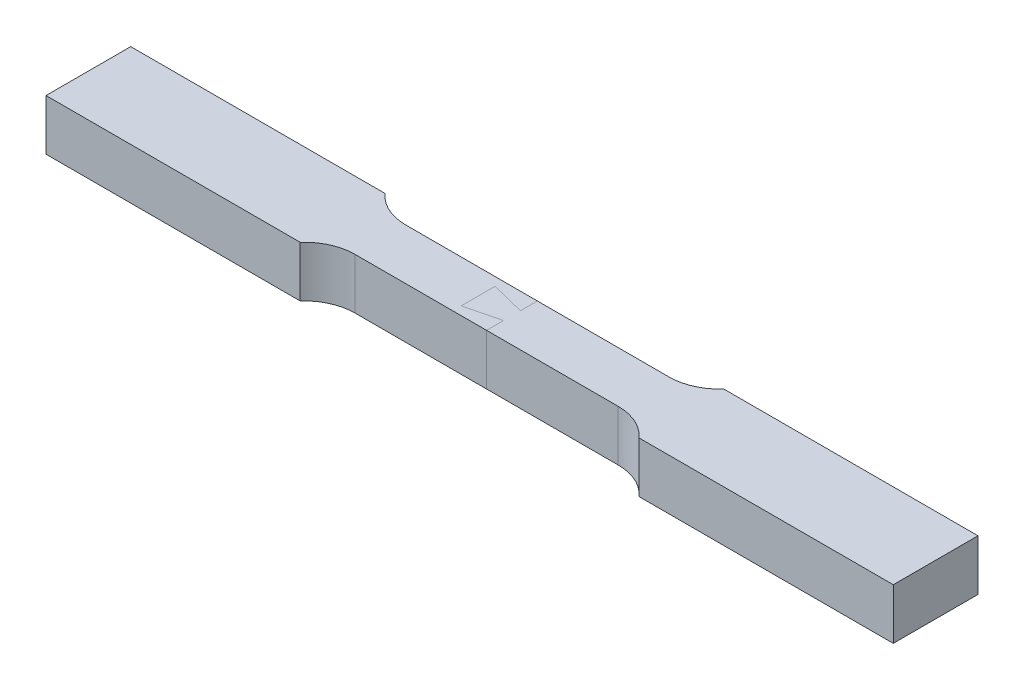
SolidWorks part; units mm, degrees
ref_plane "Front" through (0, 0, 0) normal (0, 0, 1) x (1, 0, 0)
ref_plane "Top" through (0, 0, 0) normal (0, 1, 0) x (1, 0, 0)
ref_plane "Right" through (0, 0, 0) normal (1, 0, 0) x (0, 0, -1)
sketch "Sketch1" plane through (0, 0, 0) normal (0, 1, 0) x (1, 0, 0)
  line L0 (0, 32.0696) -> (0, -21.7429) construction
  line L10 (15.5279, 3) -> (-15.5279, 3)
  line L11 (-4, 2) -> (0, 1)
  line L12 (-20, 5) -> (-50, 5)
  line L13 (-50, 5) -> (-50, -5)
  line L14 (-50, -5) -> (-20, -5)
  line L15 (-4, 2) -> (-4, -2)
  line L16 (-15.5279, -3) -> (15.5279, -3)
  line L17 (-50, 0) -> (0, 0) construction
  line L18 (-4, -2) -> (0, -1)
  line L19 (0, 3) -> (0, 1)
  line L20 (0, -3) -> (0, -1)
  line L21 (50, 5) -> (50, -5)
  line L22 (50, -5) -> (20, -5)
  line L23 (20, 5) -> (50, 5)
  arc A0 (-15.5279, 3) -> (-20, 5) centre (-15.5279, 9) cw
  arc A1 (-15.5279, -3) -> (-20, -5) centre (-15.5279, -9) ccw
  arc A2 (15.5279, 3) -> (20, 5) centre (15.5279, 9) ccw
  arc A3 (15.5279, -3) -> (20, -5) centre (15.5279, -9) cw
  point P17 (0, 1.0329)
  point P20 (0, 0)
  point P21 (-4.1313, 2)
  dimension "D8" = 4
  dimension "D4" = 6
  dimension "D1" = 50
  dimension "D2" = 30
  dimension "D3" = 6
  dimension "D5" = 10
  dimension "D6" = 1
  dimension "D7" = 2
extrude "Boss-Extrude1" add sketch "Sketch1" along normal blind 6 contours L12 L14 region at (-28.4823, 0, 0)
extrude "Boss-Extrude2" add sketch "Sketch1<4>" along normal blind 6 separate body contours L16 A3 L22 L21 L23 A2 L10 L19 L11 L15 L18 L20 region at (26.9198, 0, 0)
sketch "Sketch1<4>" plane through (0, 0, 0) normal (0, 1, 0) x (1, 0, 0) same geometry as "Sketch1"
equation "\"SectionLength\"=10"
equation "\"IntermediateLength\"=12.5"
equation "\"TotalLength\"=15"
equation "\"TotalWidth\"=4"
equation "\"DovetailRadius\"=0.25"
